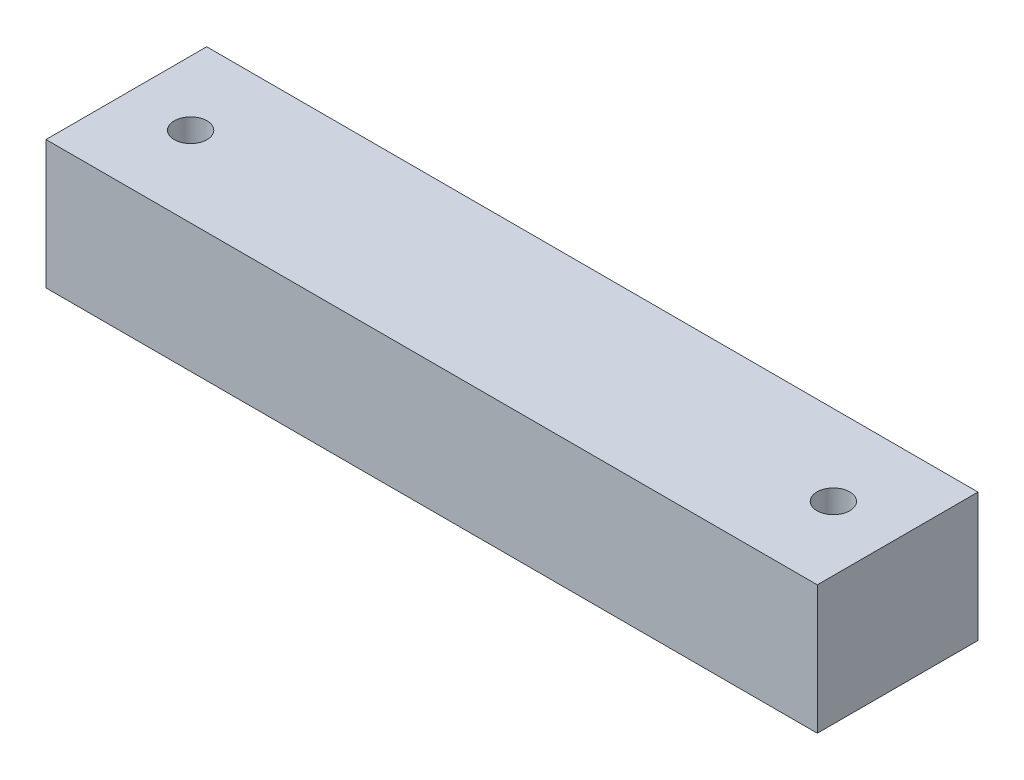
SolidWorks part; units mm, degrees
ref_plane "Front Plane" through (0, 0, 0) normal (0, 0, 1) x (1, 0, 0)
ref_plane "Top Plane" through (0, 0, 0) normal (0, 1, 0) x (1, 0, 0)
ref_plane "Right Plane" through (0, 0, 0) normal (1, 0, 0) x (0, 0, -1)
sketch "Sketch1" plane through (0, 0, 0) normal (0, 1, 0) x (1, 0, 0)
  line L1 (0, 0) -> (240, 0)
  line L2 (0, 0) -> (0, -50)
  line L3 (0, -50) -> (240, -50)
  line L4 (240, 0) -> (240, -50)
  dimension "D1" = 50
  dimension "D2" = 240
extrude "Boss-Extrude1" add sketch "Sketch1" along normal blind 40
hole_wizard "M12x1.75 Tapped Hole1" positions "Sketch2" profile "Sketch3" tap size "M12x1.75" standard "ANSI Metric"
sketch "Sketch2" plane through (0, 40, 0) normal (0, 1, 0) x (1, 0, 0)
  line L0 (0, 0) -> (0, -50) construction
  line L1 (0, -50) -> (240, -50) construction
  line L2 (240, -50) -> (240, 0) construction
  point P0 (20, -25)
  point P2 (220, -25)
  point P11 (0, 0)
  dimension "D1" = 20
  dimension "D2" = 25
  dimension "D3" = 20
sketch "Sketch3" plane through (20, 40, 25) normal (1, 0, 0) x (0, 0, 1)
  line L0 (0, 0) -> (0, 23.0644)
  line L1 (0, 23.0644) -> (5.1, 20)
  line L2 (5.1, 20) -> (5.1, 0)
  line L5 (5.1, 0) -> (0, 0)
  line L10 (0, 23.0644) -> (-5.1, 20) construction
  line L11 (0, -6.35) -> (0, 107.95) construction
  dimension "Tap Drill Dia." = 10.2
  dimension "Tap Drill Depth" = 20
  dimension "Drill Angle" = 118
cosmetic thread "Hole Thread1"
cosmetic thread "Hole Thread2"
